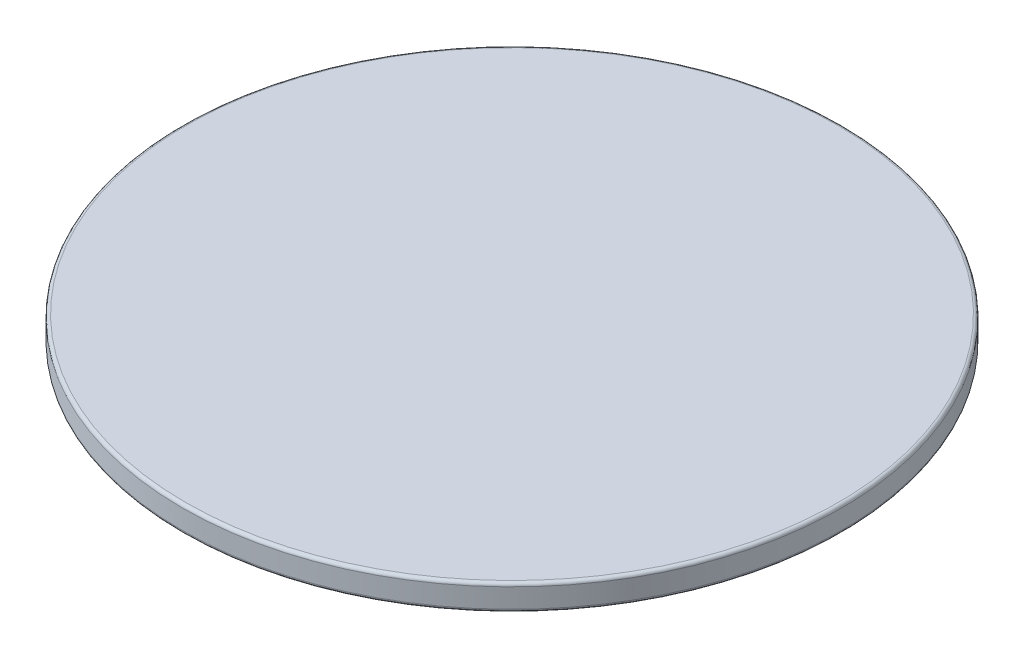
SolidWorks part; units mm, degrees
ref_plane "Front" through (0, 0, 0) normal (0, 0, 1) x (1, 0, 0)
ref_plane "Top" through (0, 0, 0) normal (0, 1, 0) x (1, 0, 0)
ref_plane "Right" through (0, 0, 0) normal (1, 0, 0) x (0, 0, -1)
sketch "Sketch2" plane through (0, 0, 0) normal (0, 1, 0) x (1, 0, 0)
  circle A0 centre (0, 0) radius 64.77
  dimension "D1" = 129.54
extrude "Boss-Extrude1" add sketch "Sketch2" along normal blind 5.08
fillet "Fillet1" radius 0.635 2 edges at (0, 0, 64.77) (0, 5.08, 64.77)
